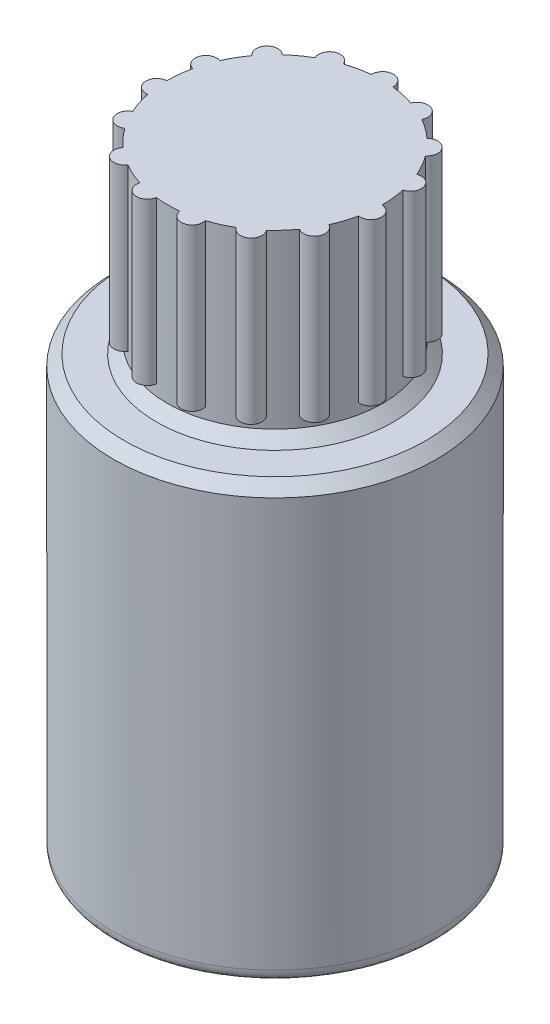
SolidWorks part; units mm, degrees
ref_plane "Front Plane" through (0, 0, 0) normal (0, 0, 1) x (1, 0, 0)
ref_plane "Top Plane" through (0, 0, 0) normal (0, 1, 0) x (1, 0, 0)
ref_plane "Right Plane" through (0, 0, 0) normal (1, 0, 0) x (0, 0, -1)
sketch "Sketch1" plane through (0, 0, 0) normal (0, 0, 1) x (1, 0, 0)
  line L0 (15, 0) -> (15, 40)
  line L1 (15, 40) -> (10, 40)
  line L2 (10, 40) -> (10, 57)
  line L3 (10, 57) -> (0, 57)
  line L4 (12, 0) -> (12, 37)
  line L5 (12, 37) -> (0, 37)
  line L6 (0, 57) -> (0, 37)
  line L7 (12, 37) -> (10, 37) construction
  line L8 (12, 0) -> (15, 0)
  dimension "D1" = 3
  dimension "D2" = 12
  dimension "D3" = 10
  dimension "D4" = 40
  dimension "D5" = 20
revolve "Revolve1" add sketch "Sketch1" angle 360 about L6
ref_axis "Axis1" through (0, 0, 0) along (0, 1, 0)
chamfer "Chamfer1" distance 1 angle 45 3 edges at (-10, 40, 0) (-15, 40, 0) (-12, 0, 0)
fillet "Fillet1" radius 1 1 edges at (-15, 0, 0) curvature continuous yes
sketch "Sketch2" plane through (0, 57, 0) normal (0, 1, 0) x (1, 0, 0)
  circle A0 centre (0, 10) radius 1
  circle A1 centre (0, 0) radius 10 construction
  circle A2 centre (0, 0) radius 10 construction
  dimension "D1" = 2
extrude "Boss-Extrude1" add sketch "Sketch2" against normal blind 15
pattern_circular "CirPattern1" count 15 over 360 about axis through (0, 0, 0) along (0, 1, 0) of "Boss-Extrude1"
